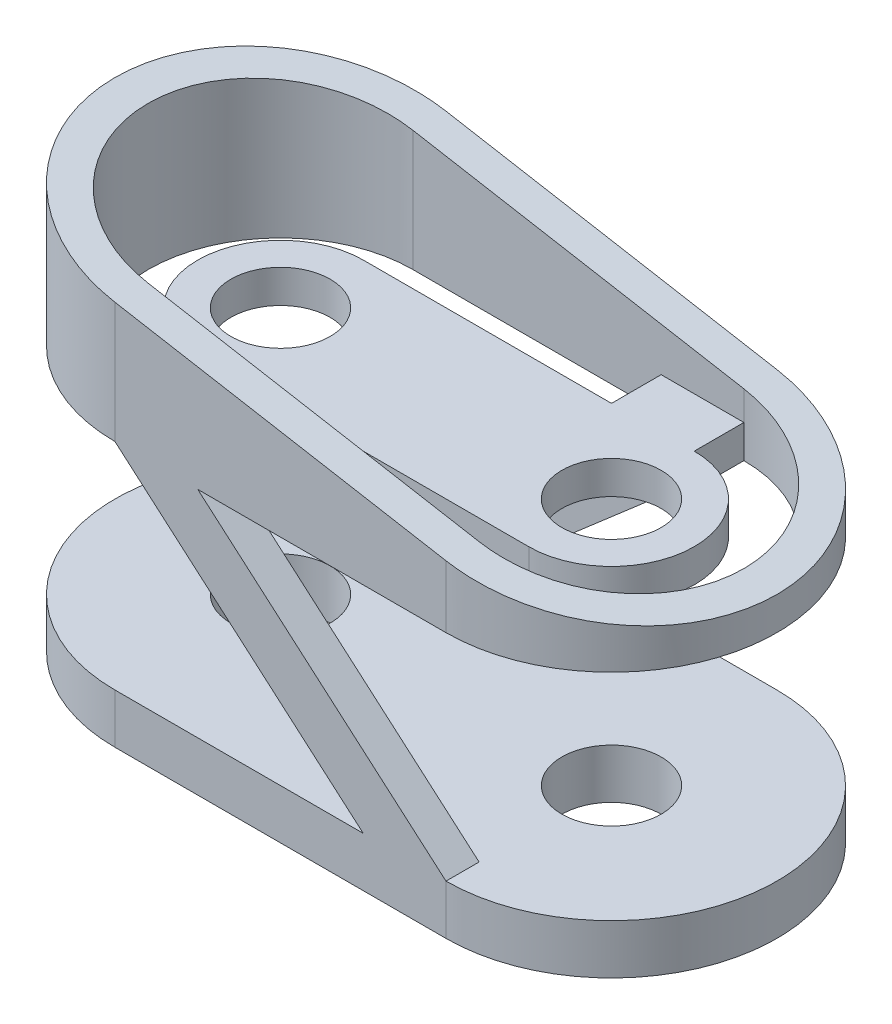
SolidWorks part; units mm, degrees
ref_plane "Front Plane" through (0, 0, 0) normal (0, 0, 1) x (1, 0, 0)
ref_plane "Top Plane" through (0, 0, 0) normal (0, 1, 0) x (1, 0, 0)
ref_plane "Right Plane" through (0, 0, 0) normal (1, 0, 0) x (0, 0, -1)
sketch "Sketch1" plane through (0, 0, 0) normal (0, 1, 0) x (1, 0, 0)
  line L0 (-50, 0) -> (50, 0) construction
  line L1 (-50, 50) -> (50, 50)
  line L2 (-50, -50) -> (50, -50)
  arc A0 (-50, 50) -> (-50, -50) centre (-50, 0) ccw
  arc A1 (50, -50) -> (50, 50) centre (50, 0) ccw
  circle A2 centre (-50, 0) radius 15
  circle A3 centre (50, 0) radius 15
  point P2 (0, 0)
  dimension "D2" = 50
  dimension "D3" = 30
  dimension "D1" = 100
extrude "Boss-Extrude1" add sketch "Sketch1" along normal blind 15
extrude "Boss-Extrude2" add sketch "Sketch1<2>" along normal blind 75 from offset 80 separate body contours L2 A1 L1 A0
sketch "Sketch1<2>" plane through (0, 0, 0) normal (0, 1, 0) x (1, 0, 0) same geometry as "Sketch1"
sketch "Sketch2" plane through (0, 0, 0) normal (0, 0, 1) x (1, 0, 0)
  line L0 (100, 90) -> (-100, 125.2654)
  line L1 (100, 80) -> (100, 155) construction
  line L2 (-100, 155) -> (-100, 80) construction
  line L3 (-50, 80) -> (50, 80) construction
  dimension "D1" = 10
  dimension "D2" = 10
extrude "Cut-Extrude1" cut sketch "Sketch2" against normal through all both and the other way through all flip side to cut
sketch "Sketch3" plane through (0, 80, 0) normal (0, -1, 0) x (1, 0, 0)
  line L4 (-50, -40) -> (50, -40)
  line L5 (50, 40) -> (-50, 40)
  line L6 (-50, -40) -> (50, -40)
  line L7 (50, 40) -> (-50, 40)
  arc A4 (-50, 40) -> (-50, -40) centre (-50, 0) ccw
  arc A5 (50, -40) -> (50, 40) centre (50, 0) ccw
  arc A6 (-50, 40) -> (-50, -40) centre (-50, 0) ccw
  arc A7 (50, -40) -> (50, 40) centre (50, 0) ccw
  dimension "D1" = 10
extrude "Cut-Extrude2" cut sketch "Sketch3" against normal blind 75
sketch "Sketch5" plane through (0, 80, 0) normal (0, -1, 0) x (1, 0, 0)
  line L0 (-50, 0) -> (50, 0) construction
  line L1 (-25, 25) -> (50, 25)
  line L2 (-50, -25) -> (25, -25)
  line L3 (50, -25) -> (50, -40)
  line L4 (50, -40) -> (25, -40)
  line L5 (-50, -40) -> (50, -40) construction
  line L6 (25, -40) -> (25, -25)
  line L7 (-50, 25) -> (-50, 40)
  line L8 (-50, 40) -> (-25, 40)
  line L9 (50, 40) -> (-50, 40) construction
  line L10 (-25, 40) -> (-25, 25)
  arc A0 (-50, 25) -> (-50, -25) centre (-50, 0) ccw
  arc A1 (50, -25) -> (50, 25) centre (50, 0) ccw
  circle A2 centre (-50, 0) radius 15 construction
  circle A3 centre (-50, 0) radius 15
  circle A4 centre (50, 0) radius 15 construction
  circle A5 centre (50, 0) radius 15
  point P2 (0, 0)
  dimension "D1" = 25
  dimension "D2" = 25
  dimension "D3" = 25
extrude "Boss-Extrude3" add sketch "Sketch5" against normal blind 10
sketch "Sketch6" plane through (0, 0, -50) normal (0, 0, -1) x (-1, 0, 0)
  line L0 (50, 15) -> (-25, 80)
  line L1 (-50, 15) -> (50, 15) construction
  line L2 (50, 80) -> (-50, 80) construction
  line L3 (-25, 80) -> (-50, 80)
  line L4 (-50, 80) -> (25, 15)
  line L5 (25, 15) -> (50, 15)
  dimension "D1" = 25
  dimension "D2" = 25
  dimension "D3" = 125
extrude "Boss-Extrude4" add sketch "Sketch6" against normal blind 10
sketch "Sketch7" plane through (0, 0, 50) normal (0, 0, 1) x (1, 0, 0)
  line L0 (50, 15) -> (-25, 80)
  line L1 (-25, 80) -> (-50, 80)
  line L2 (-50, 80) -> (25, 15)
  line L3 (-50, 15) -> (50, 15) construction
  line L4 (25, 15) -> (50, 15)
extrude "Boss-Extrude5" add sketch "Sketch7" against normal blind 10
